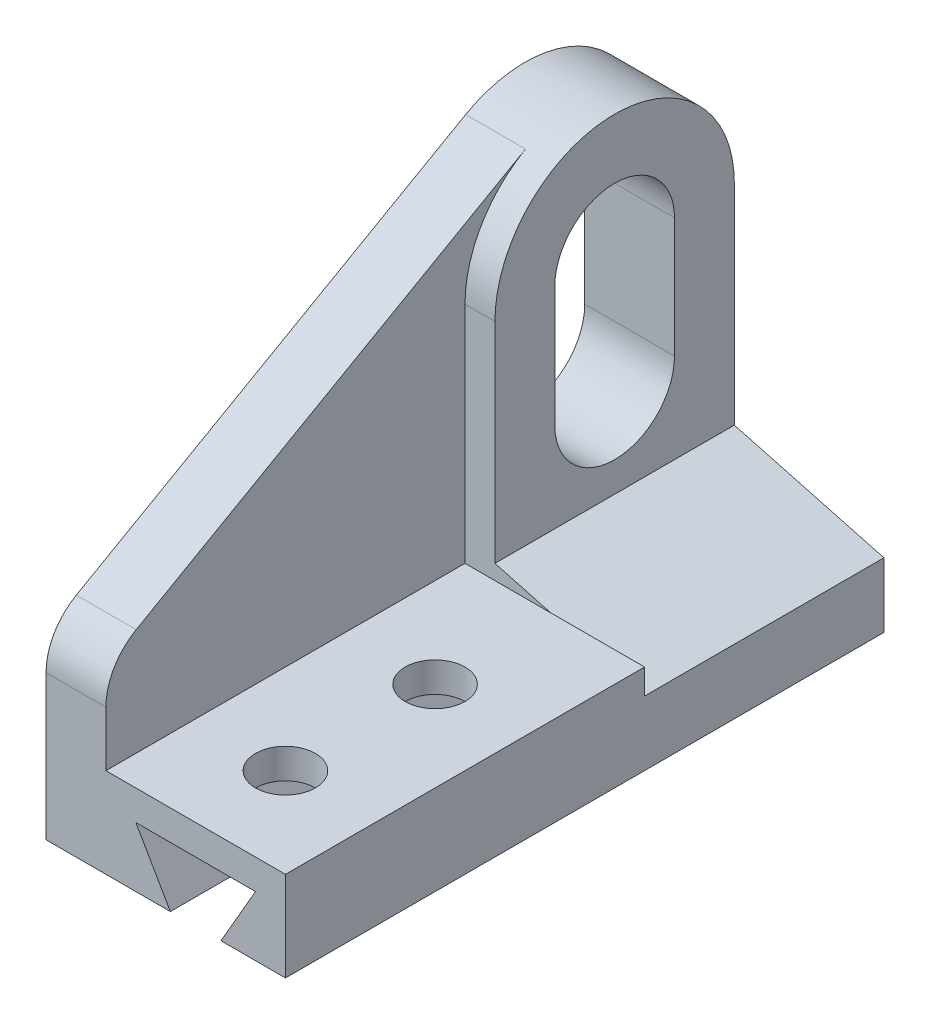
SolidWorks part; units mm, degrees
ref_plane "Front Plane" through (0, 0, 0) normal (0, 0, 1) x (1, 0, 0)
ref_plane "Top Plane" through (0, 0, 0) normal (0, 1, 0) x (1, 0, 0)
ref_plane "Right Plane" through (0, 0, 0) normal (1, 0, 0) x (0, 0, -1)
sketch "Sketch1" plane through (0, 0, 0) normal (1, 0, 0) x (0, 0, -1)
  line L0 (0, 0) -> (127, 0)
  line L1 (0, 0) -> (0, 30.7135)
  line L2 (127, 0) -> (127, 66.675)
  line L3 (76.2, 19.05) -> (76.2, 66.675)
  line L4 (76.2, 41.275) -> (127, 41.275) construction
  line L5 (76.2, 66.675) -> (127, 66.675) construction
  line L6 (88.9, 41.275) -> (88.9, 66.675)
  line L7 (114.3, 66.675) -> (114.3, 41.275)
  line L8 (6.4203, 41.7523) -> (89.0407, 88.7527)
  line L9 (0, 19.05) -> (76.2, 19.05)
  line L10 (76.2, 22.225) -> (127, 22.225)
  arc A0 (0, 30.7135) -> (6.4203, 41.7523) centre (12.7, 30.7135) cw
  arc A1 (127, 66.675) -> (76.2, 66.675) centre (101.6, 66.675) ccw
  circle A2 centre (101.6, 66.675) radius 12.7
  circle A3 centre (101.6, 41.275) radius 12.7
  point P20 (0, 38.1)
  dimension "D6" = 25.4
  dimension "D7" = 25.4
  dimension "D9" = 12.7
  dimension "D1" = 127
  dimension "D2" = 38.1
  dimension "D3" = 50.8
  dimension "D4" = 41.275
  dimension "D5" = 25.4
  dimension "D8" = 25.4
  dimension "D10" = 19.05
  dimension "D11" = 25.4
  dimension "D12" = 25.4
  dimension "D13" = 22.225
extrude "Boss-Extrude1" add sketch "Sketch1" along normal blind 12.7 contours L9 L1 L0 L2 | L2 A1 L3 L9 A3 L6 A2 L7 | A1 L8 A0 L1 L9 L3 region at (0, 10.2195, -65.8813) region at (0, 41.7815, -45.3667) region at (0, 23.0887, -101.6)
extrude "Boss-Extrude2" add sketch "Sketch1<3>" along normal blind 50.8 contours L9 L1 L0 L2 region at (0, 10.2195, -65.8813)
sketch "Sketch1<3>" plane through (0, 0, 0) normal (1, 0, 0) x (0, 0, -1) same geometry as "Sketch1"
extrude "Boss-Extrude3" add sketch "Sketch1<7>" along normal blind 19.05 contours L2 A1 L3 L9 A3 L6 A2 L7 region at (0, 23.0887, -101.6)
sketch "Sketch1<7>" plane through (0, 0, 0) normal (1, 0, 0) x (0, 0, -1) same geometry as "Sketch1"
sketch "Sketch3" plane through (0, 0, 0) normal (0, 0, 1) x (1, 0, 0)
  line L0 (37.1177, 0) -> (44.45, 12.7)
  line L1 (50.8, 0) -> (0, 0) construction
  line L2 (44.45, 12.7) -> (19.05, 12.7)
  line L3 (19.05, 12.7) -> (26.3823, 0)
  line L4 (50.8, 19.05) -> (12.7, 19.05) construction
  line L5 (31.75, 19.05) -> (31.75, 0) construction
  point P4 (31.75, 12.7)
  point P9 (31.75, 19.05)
  dimension "D1" = 25.4
  dimension "D2" = 12.7
  dimension "D3" = 60
  dimension "D4" = 60
extrude "Cut-Extrude1" cut sketch "Sketch3" against normal through all
sketch "Sketch4" plane through (0, 19.05, 0) normal (0, 1, 0) x (1, 0, 0)
  line L0 (31.75, 0) -> (31.75, 62.4107) construction
  line L1 (50.8, 0) -> (12.7, 0) construction
  line L2 (19.05, 88.9) -> (19.05, 114.3) construction
  circle A0 centre (31.75, 19.05) radius 6.35
  circle A1 centre (31.75, 50.8) radius 6.35
  point P8 (19.05, 101.6)
  dimension "D1" = 12.7
  dimension "D2" = 31.75
  dimension "D3" = 50.8
extrude "Cut-Extrude2" cut sketch "Sketch4" against normal through all
sketch "Sketch5" plane through (0, 0, -127) normal (0, 0, -1) x (-1, 0, 0)
  line L0 (-19.05, 22.225) -> (-50.8, 13.7176)
  line L1 (-50.8, 0) -> (-50.8, 22.225) construction
  line L2 (-19.05, 22.225) -> (-19.05, 66.675) construction
  line L4 (-26.3823, 0) -> (0, 0) construction
  line L5 (-50.8, 13.7176) -> (-50.8, 22.225)
  line L6 (-50.8, 22.225) -> (-19.05, 22.225)
  dimension "D1" = 105
  dimension "D2" = 22.225
extrude "Cut-Extrude3" cut sketch "Sketch5" against normal blind 50.8
